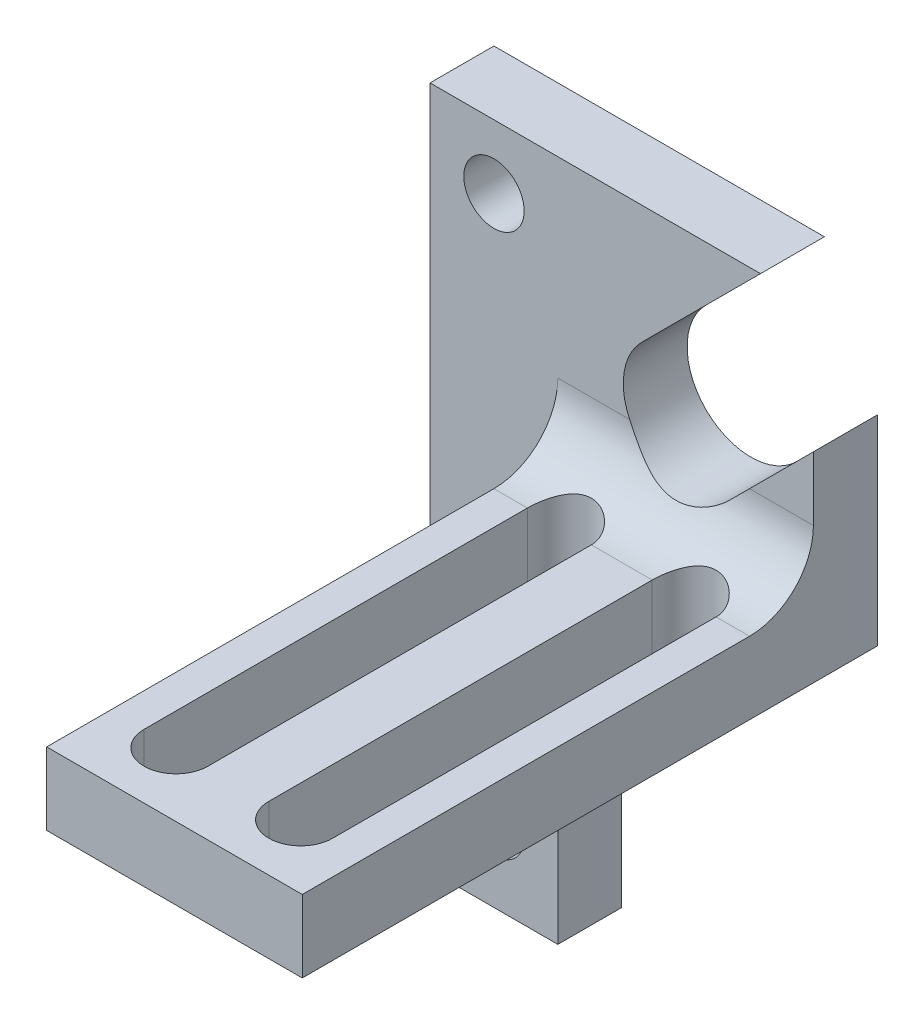
SolidWorks part; units mm, degrees
ref_plane "Front Plane" through (0, 0, 0) normal (0, 0, 1) x (1, 0, 0)
ref_plane "Top Plane" through (0, 0, 0) normal (0, 1, 0) x (1, 0, 0)
ref_plane "Right Plane" through (0, 0, 0) normal (1, 0, 0) x (0, 0, -1)
sketch "Sketch1" plane through (0, 0, 0) normal (0, 0, 1) x (1, 0, 0)
  line L9 (-13.0627, -20.833) -> (-5.0038, -12.774)
  line L16 (-5.0038, -12.774) -> (-5.0038, -25.474)
  line L17 (-5.0038, -25.474) -> (-30.4038, -25.474)
  line L18 (-30.4038, -25.474) -> (-30.4038, -0.074)
  line L20 (-30.4038, -0.074) -> (-10.2643, -0.074)
  line L21 (-22.043, -11.8527) -> (-10.2643, -0.074)
  line L22 (-30.4038, -25.474) -> (-30.4038, -28.649)
  line L23 (-30.4038, -28.649) -> (-30.4038, -32.6643)
  line L24 (-5.0038, -28.649) -> (-5.0038, -25.474)
  line L25 (-30.4038, -25.474) -> (-5.0038, -25.474)
  line L26 (-30.4038, -32.6643) -> (-5.0038, -32.6643)
  line L27 (-5.0038, -32.6643) -> (-5.0038, -28.649)
  arc A4 (-22.043, -11.8527) -> (-13.0627, -20.833) centre (-17.5529, -16.3428) ccw
  point P0 (-22.0307, -22.6928)
  dimension "D3" = 6.35
  dimension "D5" = 10.2643
  dimension "D1" = 25.4
  dimension "D2" = 3.175
  dimension "D4" = 5.0038
  dimension "D6" = 13.0627
  dimension "D7" = 17.5529
  dimension "D8" = 22.043
  dimension "D9" = 0.074
  dimension "D10" = 32.2612
extrude "Boss-Extrude2" add sketch "Sketch1" along normal blind 6.35 contours L18 L20 L21 A4 L9 L16 L17
extrude "Boss-Extrude3" add sketch "Sketch1<5>" along normal blind 57.15 contours L22 L23 L26 L27 L24 L17
sketch "Sketch1<5>" plane through (0, 0, 0) normal (0, 0, 1) x (1, 0, 0) same geometry as "Sketch1"
sketch "Sketch2" plane through (0, -25.474, 0) normal (0, 1, 0) x (1, 0, 0)
  line L0 (-17.7038, -57.15) -> (-17.7038, -6.35)
  line L3 (-5.0038, -57.15) -> (-30.4038, -57.15) construction
  line L4 (-5.0038, -6.35) -> (-30.4038, -6.35) construction
  line L6 (-8.3297, -50.8) -> (-8.3297, -12.7)
  line L10 (-14.6797, -50.8) -> (-14.6797, -12.7)
  line L12 (-20.7279, -50.8) -> (-20.7279, -12.7)
  line L13 (-27.0779, -50.8) -> (-27.0779, -12.7)
  line L14 (-5.0038, -57.15) -> (-5.0038, -6.35) construction
  arc A0 (-27.0779, -50.8) -> (-20.7279, -50.8) centre (-23.9029, -50.8) ccw
  arc A1 (-27.0779, -12.7) -> (-20.7279, -12.7) centre (-23.9029, -12.7) cw
  arc A2 (-8.3297, -12.7) -> (-14.6797, -12.7) centre (-11.5047, -12.7) ccw
  arc A3 (-8.3297, -50.8) -> (-14.6797, -50.8) centre (-11.5047, -50.8) cw
  point P15 (-8.3297, -31.75)
  point P16 (-14.6797, -31.75)
  point P20 (-20.7279, -31.75)
  point P22 (-27.0779, -31.75)
  dimension "D3" = 6.5009
  dimension "D1" = 6.35
  dimension "D2" = 3.175
  dimension "D4" = 6.35
extrude "Cut-Extrude1" cut sketch "Sketch2" against normal through all contours A2 L10 A3 L6 | A0 L12 A1 L13
fillet "Fillet1" radius 6.35 1 edges at (-17.7038, -25.474, 6.35) type face fillet first side face at (-11.5047, -25.474, 31.75) second side face at (-17.2393, -14.4351, 6.35)
sketch "Sketch6" plane through (0, 0, 0) normal (0, 0, -1) x (-1, 0, 0)
  line L0 (30.4038, -0.074) -> (43.1038, -0.074)
  line L3 (43.1038, -0.074) -> (43.1038, -10.7233)
  line L4 (43.1038, -10.7233) -> (43.1038, -67.8733)
  line L5 (43.1038, -67.8733) -> (30.4038, -67.8733)
  line L6 (30.4038, -67.8733) -> (30.4038, -32.6643)
  line L7 (30.4038, -0.074) -> (30.4038, -32.6643)
  circle A0 centre (36.7538, -6.424) radius 3
  circle A1 centre (36.7538, -60.424) radius 3
  point P13 (36.7538, -67.8733)
  dimension "D2" = 6
  dimension "D5" = 6
  dimension "D9" = 8.9803
  dimension "D1" = 12.7
  dimension "D3" = 54
  dimension "D4" = 6.35
  dimension "D6" = 12.7
  dimension "D7" = 57.15
  dimension "D8" = 35.209
  dimension "D10" = 9.7885
extrude "Boss-Extrude4" add sketch "Sketch6" against normal blind 6.35 contours L4 L5 L6 L7 L0 L3
extrude "Cut-Extrude2" cut sketch "Sketch6<3>" against normal through all contours A1 | A0
sketch "Sketch6<3>" plane through (0, 0, 0) normal (0, 0, -1) x (-1, 0, 0) same geometry as "Sketch6"
